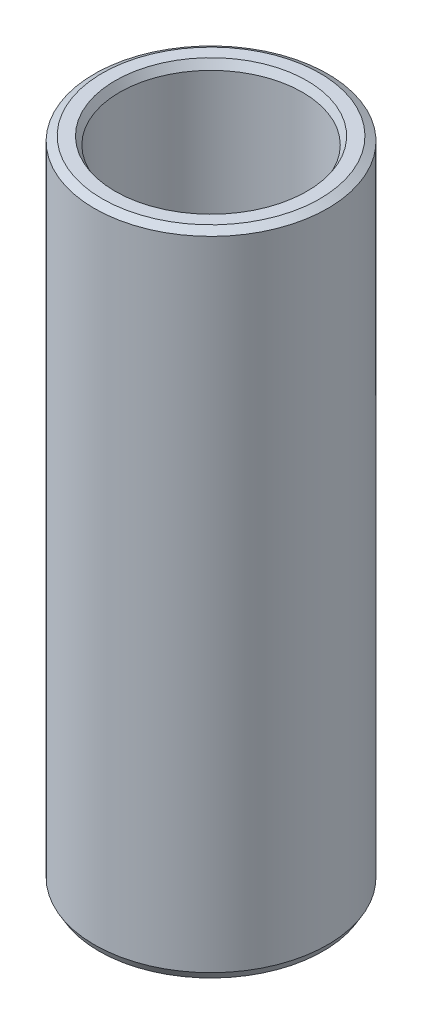
SolidWorks part; units mm, degrees
ref_plane "Front Plane" through (0, 0, 0) normal (0, 0, 1) x (1, 0, 0)
ref_plane "Top Plane" through (0, 0, 0) normal (0, 1, 0) x (1, 0, 0)
ref_plane "Right Plane" through (0, 0, 0) normal (1, 0, 0) x (0, 0, -1)
sketch "Sketch1" plane through (0, 0, 0) normal (0, 1, 0) x (1, 0, 0)
  circle A0 centre (0, 0) radius 52.5
  dimension "SLEEVE_OD" = 105
extrude "Boss-Extrude1" add sketch "Sketch1" along normal blind 292.5522
sketch "Sketch2" plane through (0, 0, 0) normal (0, 1, 0) x (1, 0, 0)
  circle A0 centre (0, 0) radius 41.1384
  dimension "BORE_D" = 82.2768
extrude "Cut-Extrude1" cut sketch "Sketch2" along normal through all
chamfer "Chamfer1" distance 2.0247 angle 60 4 edges at (0, 292.5522, 41.1384) (0, 0, 41.1384) (0, 0, 52.5) (0, 292.5522, 52.5) first distance on face at (0, 292.5522, 41.1384) first distance on face at (0, 0, 41.1384) first distance on face at (0, 292.5522, 52.5)
